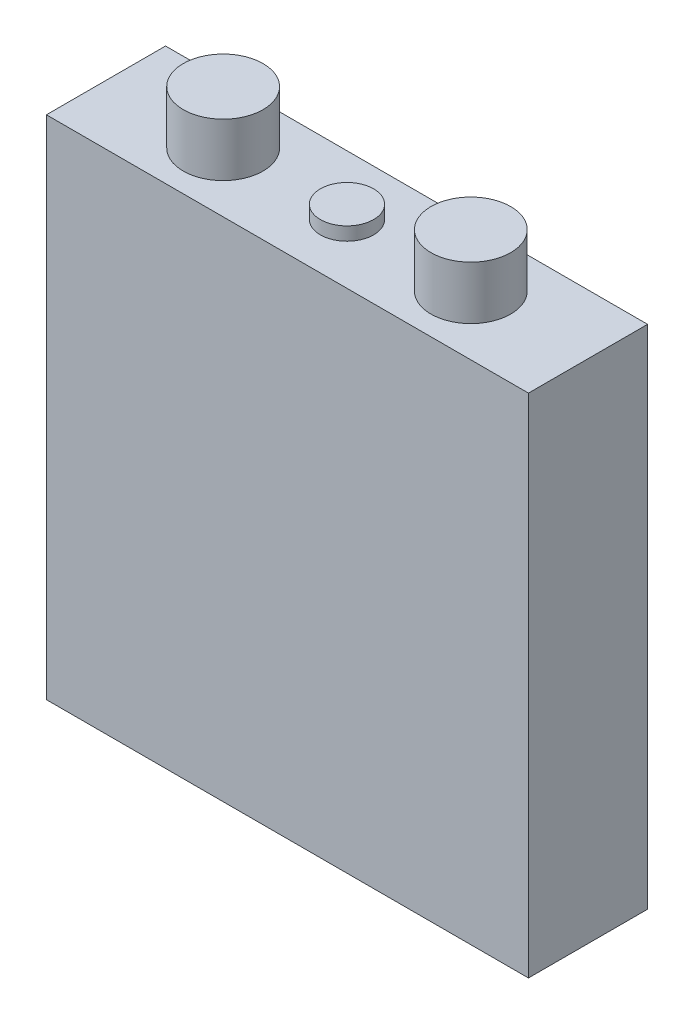
SolidWorks part; units mm, degrees
ref_plane "Front Plane" through (0, 0, 0) normal (0, 0, 1) x (1, 0, 0)
ref_plane "Top Plane" through (0, 0, 0) normal (0, 1, 0) x (1, 0, 0)
ref_plane "Right Plane" through (0, 0, 0) normal (1, 0, 0) x (0, 0, -1)
sketch "Sketch1" plane through (0, 0, 0) normal (0, 1, 0) x (1, 0, 0)
  line L1 (-69.0118, 17.0561) -> (69.0118, 17.0561)
  line L2 (-69.0118, 17.0561) -> (-69.0118, -17.0561)
  line L3 (-69.0118, -17.0561) -> (69.0118, -17.0561)
  line L4 (69.0118, 17.0561) -> (69.0118, -17.0561)
  line L5 (-69.0118, 17.0561) -> (69.0118, -17.0561) construction
  line L6 (-69.0118, -17.0561) -> (69.0118, 17.0561) construction
  point P0 (0, 0)
  dimension "D1" = 138.0236
  dimension "D2" = 34.1122
extrude "Boss-Extrude1" add sketch "Sketch1" along normal blind 145.034
sketch "Sketch2" plane through (0, 145.034, 0) normal (0, 1, 0) x (1, 0, 0)
  circle A0 centre (-35.4584, 0) radius 11.43
  circle A1 centre (35.4584, 0) radius 11.43
extrude "Boss-Extrude2" add sketch "Sketch2" along normal blind 15.24
sketch "Sketch3" plane through (0, 145.034, 0) normal (0, 1, 0) x (1, 0, 0)
  circle A0 centre (0, 0) radius 7.62
extrude "Boss-Extrude3" add sketch "Sketch3" along normal blind 3.81
